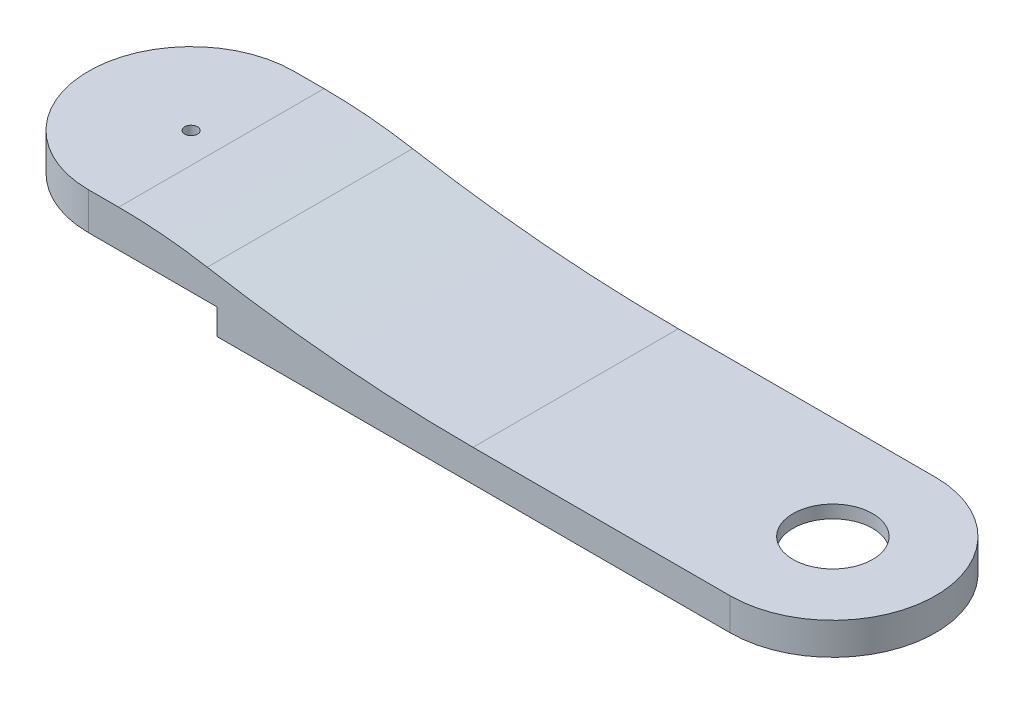
SolidWorks part; units mm, degrees
ref_plane "Front Plane" through (0, 0, 0) normal (0, 0, 1) x (1, 0, 0)
ref_plane "Top Plane" through (0, 0, 0) normal (0, 1, 0) x (1, 0, 0)
ref_plane "Right Plane" through (0, 0, 0) normal (1, 0, 0) x (0, 0, -1)
sketch "Sketch1" plane through (0, 0, 0) normal (0, 1, 0) x (1, 0, 0)
  line L0 (0, 0) -> (250, 0) construction
  line L1 (0, 29) -> (250, 29)
  line L2 (0, -40) -> (250, -40)
  line L3 (0, -29) -> (250, -29)
  line L4 (0, 40) -> (250, 40)
  arc A0 (0, 29) -> (0, -29) centre (0, 0) ccw
  arc A1 (250, -29) -> (250, 29) centre (250, 0) ccw
  arc A2 (0, 40) -> (0, -40) centre (0, 0) ccw
  arc A3 (250, -40) -> (250, 40) centre (250, 0) ccw
  dimension "D1" = 58
  dimension "D3" = 40
  dimension "D2" = 250
extrude "Boss-Extrude1" add sketch "Sketch1" along normal blind 7.5
sketch "Sketch9" plane through (0, 7.5, 0) normal (0, 1, 0) x (1, 0, 0)
  line L0 (0, -40) -> (250, -40) construction
  line L1 (250, 40) -> (0, 40) construction
  line L2 (50, -40) -> (250, -40)
  line L3 (250, 40) -> (50, 40)
  line L4 (0, 0) -> (250, 0) construction
  line L5 (50, 40) -> (50, -40)
  line L8 (50, 40) -> (50, -40)
  arc A0 (250, -40) -> (250, 40) centre (250, 0) ccw construction
  arc A1 (250, -40) -> (250, 40) centre (250, 0) ccw
  line M8 (0, 29) -> (250, 29)
  arc M9 (250, 29) -> (250, -29) centre (250, 0) cw
  line M10 (250, -29) -> (0, -29)
  arc M14 (0, -29) -> (0, 29) centre (0, 0) cw
  arc M15 (0, 40) -> (0, -40) centre (0, 0) ccw
  line M16 (0, -40) -> (250, -40)
  arc M17 (250, -40) -> (250, 40) centre (250, 0) ccw
  line M18 (250, 40) -> (0, 40)
  dimension "D1" = 200
extrude "Cut-Extrude1" cut sketch "Sketch9" against normal through all both and the other way through all contours L5 L8 M8 M14 M10 | L5 M18 M15 M16 M10 M14 M8 region at (25, 7.5, 38.7958) region at (13.3239, 7.5, 0)
extrude "Boss-Extrude3" add sketch "Sketch9<3>" along normal blind 5 contours L5 L8 M8 M10 M9 | L5 M18 M8 M9 M10 M16 M17 region at (52.5298, 7.5, 34.5) region at (161.4823, 7.5, 0)
sketch "Sketch9<3>" plane through (0, 7.5, 0) normal (0, 1, 0) x (1, 0, 0) same geometry as "Sketch9"
sketch "Sketch11" plane through (0, 7.5, 0) normal (0, -1, 0) x (1, 0, 0)
  circle A0 centre (250, 0) radius 15.5
  arc A2 (250, -29) -> (250, 29) centre (250, 0) ccw construction
  dimension "D1" = 31
extrude "Cut-Extrude2" cut sketch "Sketch11" against normal through all both and the other way through all
sketch "Sketch12" plane through (0, 12.5, 0) normal (0, 1, 0) x (1, 0, 0)
  line L0 (0, -40) -> (250, -40) construction
  line L1 (0, -29) -> (250, -29) construction
  line L2 (0, 29) -> (250, 29) construction
  line L3 (0, 40) -> (250, 40) construction
  line L4 (0, -40) -> (80, -40)
  line L5 (0, -29) -> (80, -29)
  line L6 (0, 29) -> (80, 29)
  line L7 (0, 40) -> (80, 40)
  line L8 (80, 40) -> (80, -40)
  line L10 (50, 40) -> (50, -40) construction
  arc A0 (0, 29) -> (0, -29) centre (0, 0) ccw construction
  arc A1 (0, 40) -> (0, -40) centre (0, 0) ccw construction
  arc A2 (0, 29) -> (0, -29) centre (0, 0) ccw
  arc A3 (0, 40) -> (0, -40) centre (0, 0) ccw
  line M3 (50, 40) -> (50, -40)
  line M4 (50, -40) -> (250, -40)
  line M6 (250, 40) -> (50, 40)
  dimension "D1" = 30
extrude "Boss-Extrude4" add sketch "Sketch12" along normal blind 7 contours L8 L5 M3 M4 | L7 A3 L4 L5 A2 L6 M3 | L8 L6 M6 M3 | L8 L6 L5 M3 region at (-38.7958, 12.5, 0) region at (65, 12.5, 34.5) region at (65, 12.5, 0) region at (65, 12.5, -34.5)
sketch "Sketch13" plane through (0, 19.5, 0) normal (0, 1, 0) x (1, 0, 0)
  line L3 (80, -40) -> (80, 40)
  line L4 (80, 40) -> (0, 40)
  line L5 (0, -40) -> (80, -40)
  line L6 (80, -40) -> (80, 40)
  line L7 (80, 40) -> (0, 40)
  line L8 (0, -40) -> (80, -40)
  arc A1 (0, 40) -> (0, -40) centre (0, 0) ccw
  arc A2 (0, 40) -> (0, -40) centre (0, 0) ccw
  dimension "D1" = 0
extrude "Boss-Extrude5" add sketch "Sketch13" along normal blind 5
sketch "Sketch14" plane through (0, 12.5, 0) normal (0, -1, 0) x (1, 0, 0)
  line L6 (0, -40) -> (50, -40)
  line L7 (50, -40) -> (50, -29)
  line L8 (50, -29) -> (0, -29)
  line L9 (0, 29) -> (50, 29)
  line L10 (50, 29) -> (50, 40)
  line L11 (50, 40) -> (0, 40)
  line L12 (0, -40) -> (50, -40)
  line L13 (50, -40) -> (50, -29)
  line L14 (50, -29) -> (0, -29)
  line L15 (0, 29) -> (50, 29)
  line L16 (50, 29) -> (50, 40)
  line L17 (50, 40) -> (0, 40)
  arc A2 (0, 29) -> (0, -29) centre (0, 0) ccw
  arc A3 (0, 40) -> (0, -40) centre (0, 0) ccw
  arc A4 (0, 29) -> (0, -29) centre (0, 0) ccw
  arc A5 (0, 40) -> (0, -40) centre (0, 0) ccw
  dimension "D1" = 0
extrude "Boss-Extrude6" add sketch "Sketch14" along normal blind 2.5
sketch "Sketch15" plane through (0, 19.5, 0) normal (0, -1, 0) x (1, 0, 0)
  circle A0 centre (0, 0) radius 2.5
  dimension "D1" = 5
extrude "Cut-Extrude3" cut sketch "Sketch15" against normal through all both and the other way through all
fillet "Fillet1" radius 200 1 edges at (80, 24.5, 0)
fillet "Fillet2" radius 600 1 edges at (80, 12.5, 0)
